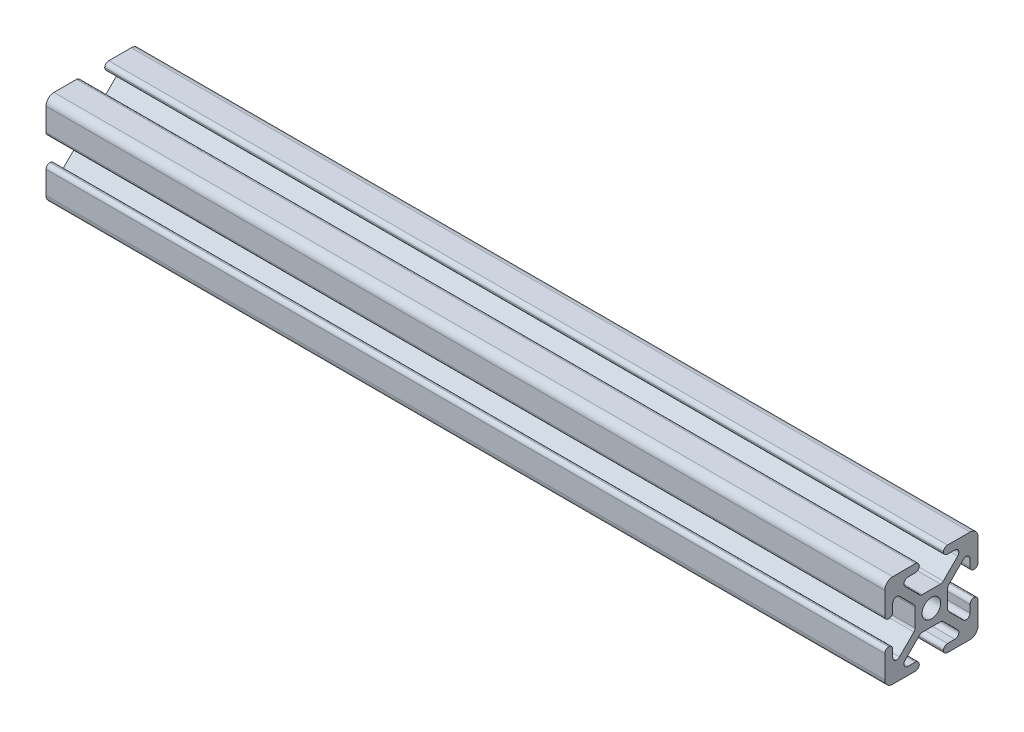
SolidWorks part; units mm, degrees
ref_plane "Front Plane" through (0, 0, 0) normal (1, 0, 0) x (0, 1, 0)
ref_plane "Top Plane" through (0, 0, 0) normal (0, 0, 1) x (0, 1, 0)
ref_plane "Right Plane" through (0, 0, 0) normal (0, 1, 0) x (-1, 0, 0)
sketch "Sketch1" plane through (0, 0, 0) normal (1, 0, 0) x (0, 1, 0)
  line L0 (0, 0) -> (0, 12.5) construction
  line L1 (-12.5, -12.5) -> (12.5, -12.5)
  line L2 (-12.5, -12.5) -> (-12.5, 12.5)
  line L3 (-12.5, 12.5) -> (12.5, 12.5)
  line L4 (12.5, -12.5) -> (12.5, 12.5)
  line L5 (-12.5, -12.5) -> (12.5, 12.5) construction
  line L6 (-12.5, 12.5) -> (12.5, -12.5) construction
  line L7 (-3.25, 12.5) -> (-3.25, 10.37)
  line L8 (-3.25, 10.37) -> (-8.8639, 10.37)
  line L9 (-8.8639, 10.37) -> (-2.8739, 4.38)
  line L10 (-2.8739, 4.38) -> (2.8739, 4.38)
  line L11 (8.8639, 10.37) -> (2.8739, 4.38)
  line L12 (3.25, 10.37) -> (8.8639, 10.37)
  line L13 (3.25, 12.5) -> (3.25, 10.37)
  line L14 (12.5, -3.25) -> (10.37, -3.25)
  line L15 (10.37, -3.25) -> (10.37, -8.8639)
  line L16 (10.37, -8.8639) -> (4.38, -2.8739)
  line L17 (4.38, 2.8739) -> (4.38, -2.8739)
  line L18 (10.37, 8.8639) -> (4.38, 2.8739)
  line L19 (10.37, 3.25) -> (10.37, 8.8639)
  line L20 (12.5, 3.25) -> (10.37, 3.25)
  line L21 (-3.25, -12.5) -> (-3.25, -10.37)
  line L22 (-3.25, -10.37) -> (-8.8639, -10.37)
  line L23 (-8.8639, -10.37) -> (-2.8739, -4.38)
  line L24 (2.8739, -4.38) -> (-2.8739, -4.38)
  line L25 (8.8639, -10.37) -> (2.8739, -4.38)
  line L26 (3.25, -10.37) -> (8.8639, -10.37)
  line L27 (3.25, -12.5) -> (3.25, -10.37)
  line L28 (-12.5, 3.25) -> (-10.37, 3.25)
  line L29 (-10.37, 3.25) -> (-10.37, 8.8639)
  line L30 (-10.37, 8.8639) -> (-4.38, 2.8739)
  line L31 (-4.38, -2.8739) -> (-4.38, 2.8739)
  line L32 (-10.37, -8.8639) -> (-4.38, -2.8739)
  line L33 (-10.37, -3.25) -> (-10.37, -8.8639)
  line L34 (-12.5, -3.25) -> (-10.37, -3.25)
  circle A0 centre (0, 0) radius 2.5
  point P0 (0, 0)
  point P15 (0, 4.38)
  dimension "D3" = 5
  dimension "D1" = 25
  dimension "D2" = 25
  dimension "D4" = 2.13
  dimension "D5" = 2.13
  dimension "D6" = 6.5
  dimension "D7" = 4.38
  dimension "D8" = 4
extrude "Boss-Extrude1" add sketch "Sketch1" along normal blind 225 contours L34 L2 L1 L21 L22 L23 L24 L25 L26 L27 L4 L14 L15 L16 L17 L18 L19 L20 L3 L13 L12 L11 L10 L9 L8 L7 L28 L29 L30 L31 L32 L33 A0 region at (0, -12.1464, -7.875)
fillet "Fillet1" radius 1.065 32 edges at (112.5, -10.37, -8.8639) (112.5, 2.8739, -4.38) (112.5, -2.8739, -4.38) (112.5, -4.38, 2.8739) (112.5, -4.38, -2.8739) (112.5, -2.8739, 4.38) (112.5, 2.8739, 4.38) (112.5, 4.38, 2.8739) (112.5, 4.38, -2.8739) (112.5, -8.8639, -10.37) (112.5, 8.8639, -10.37) (112.5, 10.37, -8.8639) (112.5, -10.37, 8.8639) (112.5, -8.8639, 10.37) (112.5, 10.37, 8.8639) (112.5, 8.8639, 10.37) (112.5, 12.5, 3.25) (112.5, -3.25, -12.5) (112.5, -10.37, 3.25) (112.5, 10.37, 3.25) (112.5, -10.37, -3.25) (112.5, -12.5, -3.25) (112.5, -12.5, 3.25) (112.5, 3.25, -10.37) (112.5, -3.25, -10.37) (112.5, 3.25, -12.5) (112.5, 10.37, -3.25) (112.5, 12.5, -3.25) (112.5, 3.25, 12.5) (112.5, 3.25, 10.37) (112.5, -3.25, 10.37) (112.5, -3.25, 12.5)
fillet "Fillet2" radius 2.13 4 edges at (112.5, 12.5, -12.5) (112.5, -12.5, -12.5) (112.5, 12.5, 12.5) (112.5, -12.5, 12.5)
